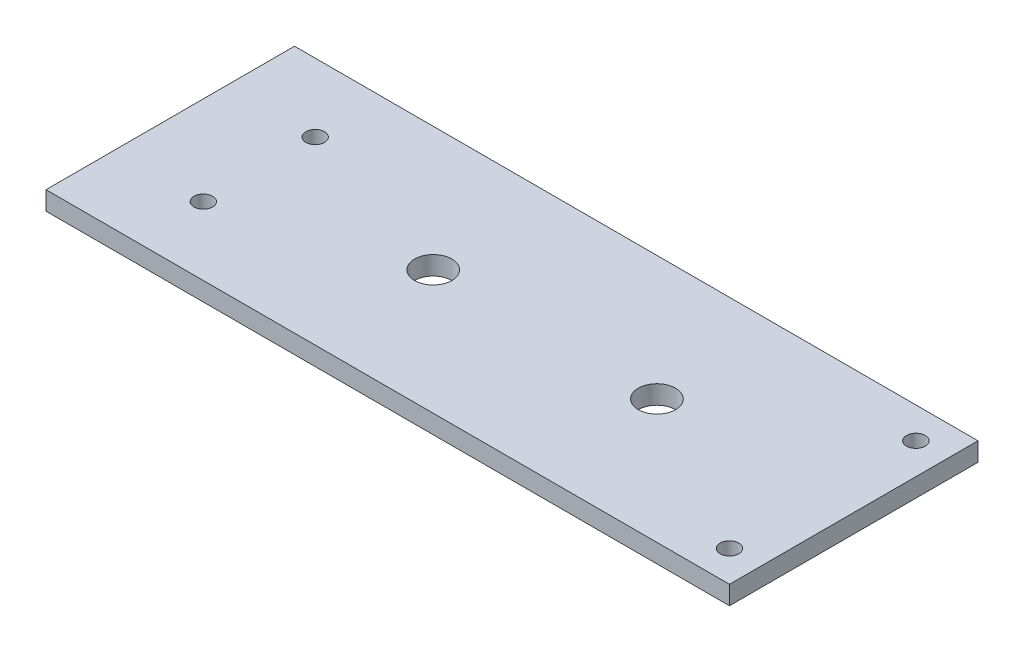
SolidWorks part; units mm, degrees
ref_plane "Front Plane" through (0, 0, 0) normal (0, 0, 1) x (1, 0, 0)
ref_plane "Top Plane" through (0, 0, 0) normal (0, 1, 0) x (1, 0, 0)
ref_plane "Right Plane" through (0, 0, 0) normal (1, 0, 0) x (0, 0, -1)
sketch "Sketch1" plane through (0, 0, 0) normal (0, 1, 0) x (1, 0, 0)
  line L0 (-67.675, 20) -> (-31.675, 20)
  line L1 (0, 0) -> (-110, 0)
  line L2 (0, 0) -> (0, 40)
  line L3 (0, 40) -> (-110, 40)
  line L4 (-110, 0) -> (-110, 40)
  circle A0 centre (-67.675, 20) radius 3
  circle A1 centre (-31.675, 20) radius 3
  circle A2 centre (-95.675, 29) radius 1.5
  circle A3 centre (-95.675, 11) radius 1.5
  circle A4 centre (-5, 35) radius 1.5
  circle A5 centre (-5, 5) radius 1.5
  dimension "D6" = 6
  dimension "D7" = 6
  dimension "D8" = 28
  dimension "D12" = 3
  dimension "D13" = 3
  dimension "D14" = 3
  dimension "D15" = 3
  dimension "D1" = 110
  dimension "D2" = 40
  dimension "D3" = 36
  dimension "D4" = 42.325
  dimension "D5" = 20
  dimension "D9" = 0
  dimension "D10" = 11
  dimension "D11" = 11
  dimension "D16" = 5
  dimension "D17" = 5
  dimension "D18" = 5
  dimension "D19" = 5
extrude "Boss-Extrude1" add sketch "Sketch1" along normal blind 3 contours L4 L1 L2 L3 A1 | A0 | A0 | A1 region at (-31.675, 0, -22.9151) region at (-70.5901, 0, -20) region at (-55, 0, -1.1705)
extrude "Cut-Extrude2" cut sketch "Sketch1<6>" along normal blind 16 contours A1 | A0 region at (-31.675, 0, -22.9151)
sketch "Sketch1<6>" plane through (0, 0, 0) normal (0, 1, 0) x (1, 0, 0) same geometry as "Sketch1"
